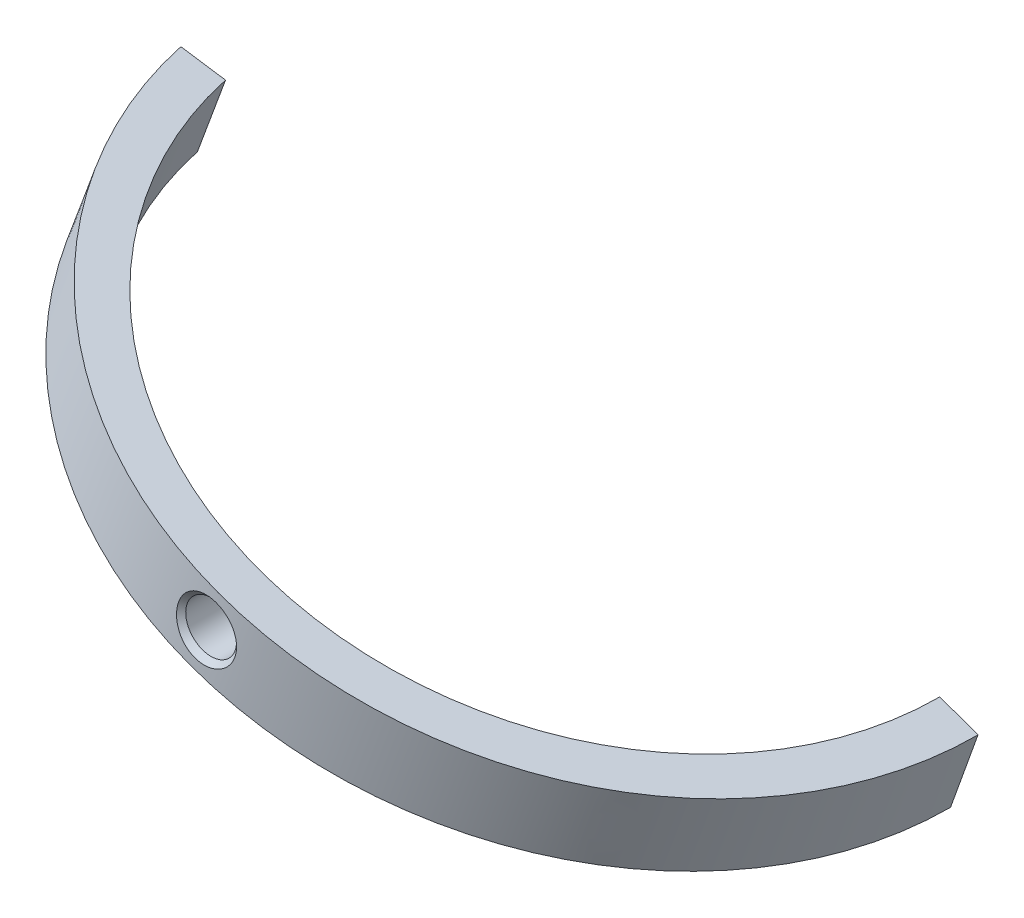
SolidWorks part; units mm, degrees
ref_plane "Přední rovina" through (0, 0, 0) normal (0, 0, 1) x (1, 0, 0)
ref_plane "Horní rovina" through (0, 0, 0) normal (0, 1, 0) x (1, 0, 0)
ref_plane "Pravá rovina" through (0, 0, 0) normal (1, 0, 0) x (0, 0, -1)
sketch "Skica1" plane through (0, 0, 0) normal (0, 0, 1) x (1, 0, 0)
  line L0 (-393.3135, -15.83) -> (-357.1063, -29.0083) construction
  line L1 (-393.3135, -15.83) -> (-357.1063, -29.0083) construction
  line L2 (-361.5866, -31.6191) -> (-358.4905, -32.7612) construction
  line L4 (-358.4668, -32.7699) -> (-357.1149, -29.0052)
  line L8 (-356.4858, -27.2532) -> (-356.8238, -28.1944) construction
  line L9 (-358.9943, -28.3211) -> (-357.1149, -29.0052)
  line L10 (-360.3433, -32.0777) -> (-358.9943, -28.3211)
  line L11 (-358.4668, -32.7699) -> (-360.3433, -32.0777)
  line L12 (-372.8806, -16.0194) -> (-374.7984, -21.2885) construction
  line L13 (-372.8806, -16.0194) -> (-374.7984, -21.2885) construction
  dimension "D2" = 2
revolve "Rotovat1" add sketch "Skica1" angle 170 about L13
hole_wizard "M3 závit1" positions "3DSkica2" profile "Skica4" tap size "M3" standard "ISO" end condition up to next
sketch3d "3DSkica2"
  line L7 (-376.5783, -26.1779, 19.2735) -> (-376.5754, -26.1698, 17.2735) construction
  line L12 (-376.5783, -26.1779, 19.2735) -> (-362.5591, -31.2804, 19.2738) construction
  line L15 (-360.3433, -32.0777, 0) -> (-358.4668, -32.7699, 0) construction
  line L16 (-376.5783, -26.1779, 19.2735) -> (-375.2102, -22.419, 19.2563) construction
  arc A4 (-394.414, -19.6862, 3.3468) -> (-358.4668, -32.7699, 0) centre (-376.578, -26.178, 0) ccw construction
  arc A5 (-392.5602, -20.3518, 2.9995) -> (-360.3433, -32.0777, 0) centre (-376.5751, -26.1699, 0) ccw construction
  arc A9 (-393.03, -15.9332, 3.3438) -> (-357.1149, -29.0052, 0) centre (-375.2099, -22.4191, 0) ccw construction
  point P36 (-369.9861, -8.0668, 0)
  point P40 (-370.6672, -9.9381, 0)
  point P76 (-368.6239, -4.3242, 0)
  point P77 (-375.8943, -24.2984, 19.2649)
  point P80 (-375.8943, -24.2984, 19.2649)
  point P82 (-375.8943, -24.2984, 19.2649)
sketch "Skica4" plane through (-375.8943, -24.2984, 19.2649) normal (0.7071, 0.7071, -0.0039) x (0.7071, -0.7071, 0.0018)
  line L0 (0, 0) -> (0, 19.3216)
  line L1 (0, 19.3216) -> (1.25, 19.3216)
  line L2 (1.25, 19.3216) -> (1.25, 0.275)
  line L3 (1.25, 0.275) -> (1.525, 0)
  line L5 (1.525, 0) -> (0, 0)
  line L6 (-1.25, 0.275) -> (-1.525, 0) construction
  line L11 (0, -6.35) -> (0, 107.95) construction
  dimension "Průměr závitníku" = 2.5
  dimension "Hloubka závitníku" = 19.3216
  dimension "Průměr blíz. kuž. zahloubení" = 3.05
  dimension "Úhel blíz. kuž. zahloubení" = 90
cosmetic thread "Závit díry5"
